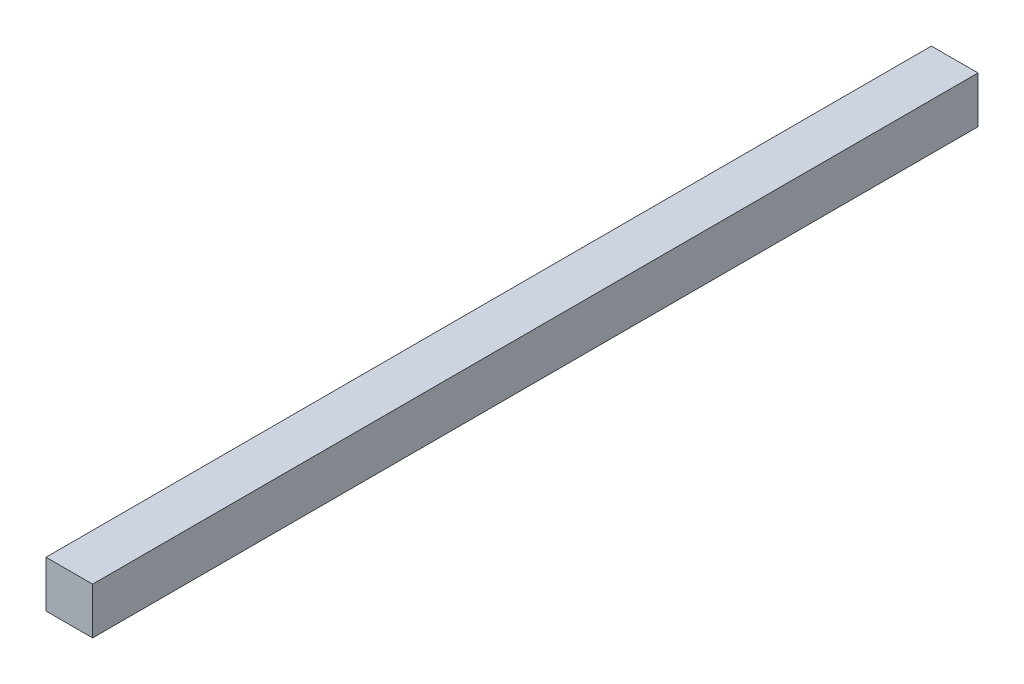
SolidWorks part; units mm, degrees
ref_plane "Ebene vorne" through (0, 0, 0) normal (0, 0, 1) x (1, 0, 0)
ref_plane "Ebene oben" through (0, 0, 0) normal (0, 1, 0) x (1, 0, 0)
ref_plane "Ebene rechts" through (0, 0, 0) normal (1, 0, 0) x (0, 0, -1)
sketch "Skizze1" plane through (0, 0, 0) normal (0, 0, 1) x (1, 0, 0)
  line L1 (0, 0) -> (50, 0)
  line L2 (0, 0) -> (0, 50)
  line L3 (0, 50) -> (50, 50)
  line L4 (50, 0) -> (50, 50)
  dimension "D1" = 50
  dimension "D2" = 50
extrude "Aufsatz-Linear austragen1" add sketch "Skizze1" along normal blind 950
